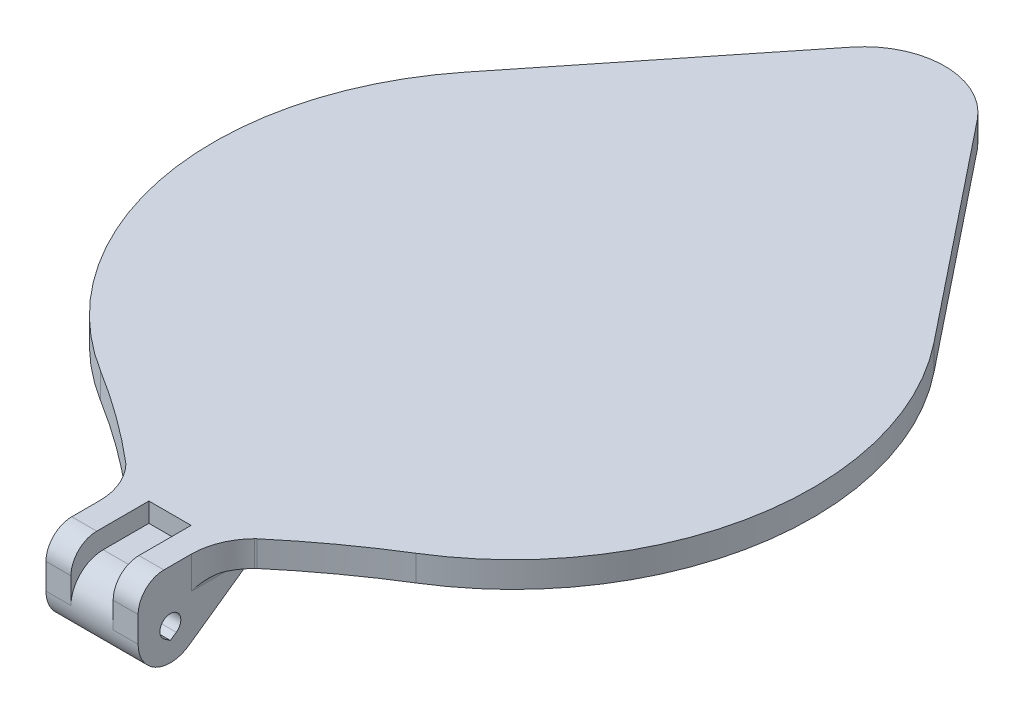
SolidWorks part; units mm, degrees
ref_plane "Front Plane" through (0, 0, 0) normal (0, 0, 1) x (1, 0, 0)
ref_plane "Top Plane" through (0, 0, 0) normal (0, 1, 0) x (1, 0, 0)
ref_plane "Right Plane" through (0, 0, 0) normal (1, 0, 0) x (0, 0, -1)
sketch "Sketch1" plane through (0, 0, 0) normal (0, 1, 0) x (1, 0, 0)
  line L2 (-9.7693, 62.2982) -> (-36.3417, 29.0092)
  line L3 (9.7693, 62.2982) -> (36.3417, 29.0092)
  circle A0 centre (0, 0) radius 46.5
  circle A2 centre (0, 54.5) radius 12.5
  dimension "D1" = 93
  dimension "D3" = 54.5
  dimension "D2" = 25
extrude "Boss-Extrude1" add sketch "Sketch1" along normal blind 4 contours A2 A0 L3 | A2 L2 A0 | A0 A2 | A2 A0 | A0 A2
sketch "Sketch5" plane through (0, 4, 0) normal (0, -1, 0) x (1, 0, 0)
  line L1 (7.15, 45.947) -> (-7.15, 45.947)
  line L2 (7.15, 45.947) -> (7.15, 61.947)
  line L3 (7.15, 61.947) -> (-7.15, 61.947)
  line L4 (-7.15, 45.947) -> (-7.15, 61.947)
  line L5 (7.15, 45.947) -> (-7.15, 61.947) construction
  line L6 (7.15, 61.947) -> (-7.15, 45.947) construction
  arc A0 (36.3417, -29.0092) -> (-36.3417, -29.0092) centre (0, 0) ccw construction
  point P0 (0, 53.947)
  dimension "D1" = 14.3
  dimension "D2" = 16
extrude "Boss-Extrude3" add sketch "Sketch5" along normal up to surface (4 mm away) up to face at (0, 0, -27.9518)
fillet "Fillet4" [suppressed] radius 12
sketch "Sketch3" plane through (0, 0, 0) normal (1, 0, 0) x (0, 0, -1)
  line L1 (-59.4225, -5.337) -> (-60.3461, -5.975)
  line L2 (-60.3461, -5.975) -> (-61.2696, -5.337)
  circle A0 centre (-60.3461, -4) radius 1.625
  dimension "D1" = 3.25
  dimension "D2" = 1.975
chamfer "Chamfer1" distance 7 angle 45 2 edges at (7.15, 2, 45.947) (-7.15, 2, 45.947)
fillet "Fillet13" radius 10 2 edges at (7.15, 2, 52.947) (-7.15, 2, 52.947)
sketch "Sketch12" plane through (0, 0, 0) normal (0, -1, 0) x (1, 0, 0)
  circle A0 centre (0, 0) radius 44
  circle A1 centre (0, 0) radius 41
  dimension "D1" = 82
  dimension "D2" = 3
extrude "Cut-Extrude7" cut sketch "Sketch12" against normal blind 2.3
sketch "Sketch9" plane through (0, 0, 0) normal (1, 0, 0) x (0, 0, -1)
  line L2 (-65.3461, 4) -> (-65.3461, -4)
  line L4 (-46, 0) -> (-57.4642, -8.0859)
  line L8 (-46, 0) -> (-46, 4)
  line L9 (-46, 4) -> (-65.3461, 4)
  line L10 (-61.947, 4) -> (-57.0891, 4) construction
  line L11 (-44, 0) -> (44, 0) construction
  circle A1 centre (-60.3461, -4) radius 5
  dimension "D1" = 10
  dimension "D2" = 2
extrude "Boss-Extrude4" add sketch "Sketch9" along normal mid plane 14.3
fillet "Fillet11" radius 1 1 edges at (0, 0, 46)
sketch "Sketch10" plane through (0, 0, 0) normal (1, 0, 0) x (0, 0, -1)
  line L0 (-60.3461, 1) -> (-53.2461, 1)
  line L1 (-53.2461, 1) -> (-53.2461, 4)
  line L2 (-57.0891, 4) -> (-65.3461, 4) construction
  line L3 (-53.2461, 4) -> (-65.3461, 4)
  line L4 (-65.3461, 4) -> (-65.3461, -4)
  circle A0 centre (-60.3461, -4) radius 5
  dimension "D2" = 7.1
extrude "Cut-Extrude4" cut sketch "Sketch10" against normal mid plane 6.55
extrude "Cut-Extrude5" cut sketch "Sketch3" against normal mid plane 44 contours A0 | A0 L2 L1
sketch "Sketch13" plane through (0, 0, 0) normal (0, -1, 0) x (1, 0, 0)
  circle A0 centre (0, -54.5) radius 9.125
  arc A1 (-9.7693, -62.2982) -> (9.7693, -62.2982) centre (0, -54.5) ccw construction
  dimension "D1" = 18.25
extrude "Cut-Extrude8" cut sketch "Sketch13" against normal blind 0.6
fillet "Fillet15" radius 1 2 edges at (-7.15, 0, 51.386) (7.15, 0, 51.386)
fillet "Fillet16" radius 120 2 edges at (-16.6989, 2, 43.3981) (16.6989, 2, 43.3981)
fillet "Fillet17" radius 3 2 edges at (-10.0789, 2, 50.0181) (10.0789, 2, 50.0181)
fillet "Fillet18" radius 4 2 edges at (-5.2125, 4, 65.3461) (5.2125, 4, 65.3461)
fillet "Fillet19" radius 1 2 edges at (0, 0, -41) (0, 0, -44)
